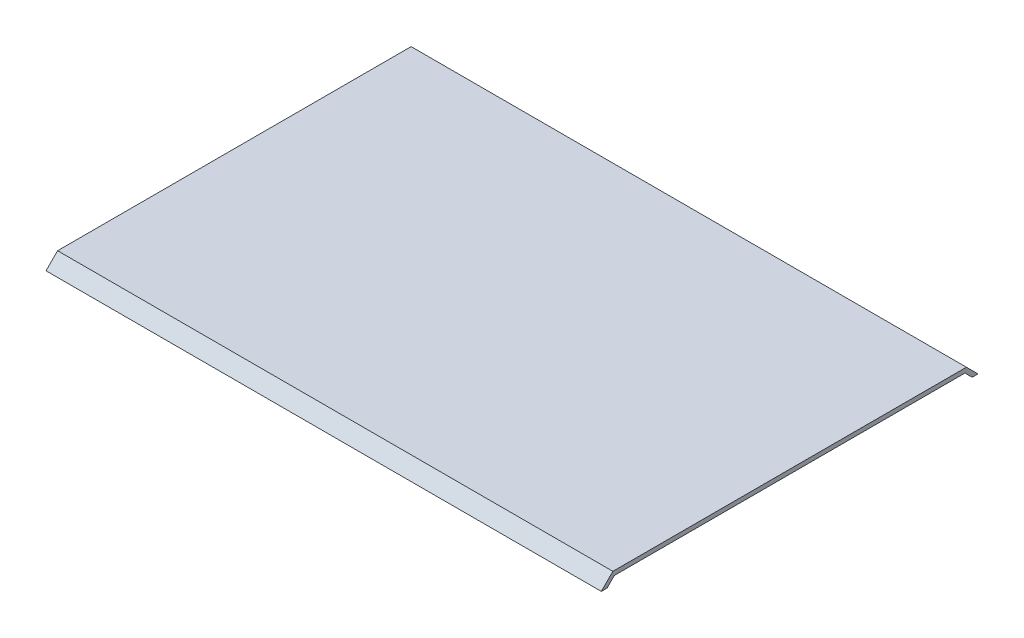
SolidWorks part; units mm, degrees
ref_plane "Front Plane" through (0, 0, 0) normal (0, 0, 1) x (1, 0, 0)
ref_plane "Top Plane" through (0, 0, 0) normal (0, 1, 0) x (1, 0, 0)
ref_plane "Right Plane" through (0, 0, 0) normal (1, 0, 0) x (0, 0, -1)
sketch "Sketch1" plane through (0, 0, 0) normal (1, 0, 0) x (0, 0, -1)
  line L7 (-82.5383, 2.54) -> (82.5383, 2.54)
  line L8 (-71.1083, -2.54) -> (-82.5383, -2.54)
  line L10 (-82.5383, 2.54) -> (-82.5383, -2.54)
  line L11 (82.5383, 2.54) -> (82.5383, -2.54)
  line L12 (82.5383, -2.54) -> (71.1083, -2.54)
  line L14 (-71.1083, -2.54) -> (-71.1083, 0.635)
  line L15 (-71.1083, 0.635) -> (71.1083, 0.635)
  line L16 (71.1083, -2.54) -> (71.1083, 0.635)
  point P9 (0, 0.635)
  point P12 (82.5383, 0)
  dimension "D1" = 1.905
  dimension "D2" = 11.43
  dimension "D5" = 165.0767
  dimension "D6" = 5.08
extrude "Boss-Extrude1" add sketch "Sketch1" along normal blind 243.332
sketch "Sketch2" plane through (0, -2.54, 0) normal (0, -1, 0) x (1, 0, 0)
  line L0 (243.332, 82.5383) -> (0, 82.5383) construction
  line L1 (8.4667, 80.6333) -> (122.7667, 80.6333)
  line L2 (8.4667, 80.6333) -> (8.4667, -80.6333)
  line L3 (8.4667, -80.6333) -> (122.7667, -80.6333)
  line L4 (122.7667, 80.6333) -> (122.7667, -80.6333)
  line L5 (0, 71.1083) -> (0, -71.1083) construction
  line L6 (131.2333, 80.6333) -> (209.4653, 80.6333)
  line L7 (131.2333, 80.6333) -> (131.2333, -80.6333)
  line L8 (131.2333, -80.6333) -> (209.4653, -80.6333)
  line L9 (209.4653, 80.6333) -> (209.4653, -80.6333)
  line L10 (217.932, 80.6333) -> (243.332, 80.6333)
  line L11 (217.932, 80.6333) -> (217.932, -80.6333)
  line L12 (217.932, -80.6333) -> (243.332, -80.6333)
  line L13 (243.332, 80.6333) -> (243.332, -80.6333)
  line L14 (243.332, 82.5383) -> (243.332, 71.1083) construction
  point P4 (8.4667, 0)
  point P17 (131.2333, 0)
  point P24 (217.932, 0)
  point P26 (209.4653, 0)
  dimension "D1" = 1.905
  dimension "D2" = 8.4667
  dimension "D3" = 8.4667
  dimension "D4" = 8.4667
  dimension "D5" = 25.4
  dimension "D7" = 114.3
extrude "Cut-Extrude1" cut sketch "Sketch2" against normal offset from surface (3.175 mm away) 1.905 up to face at (121.666, 2.54, 0)
sketch "Sketch4" plane through (0, -2.54, 0) normal (0, -1, 0) x (1, 0, 0)
  line L0 (4.2333, 78.5167) -> (7.4083, 75.3417)
  line L1 (4.2333, 78.5167) -> (1.0583, 75.3417)
  line L2 (7.4083, 75.3417) -> (4.2333, 72.1667)
  line L3 (1.0583, 75.3417) -> (4.2333, 72.1667)
  line L4 (4.2333, 78.5167) -> (4.2333, 72.1667) construction
  line L5 (7.4083, 75.3417) -> (1.0583, 75.3417) construction
  line L6 (210.5237, 75.3417) -> (213.6987, 78.5167)
  line L7 (8.4667, 71.1083) -> (0, 71.1083) construction
  line L9 (123.825, 75.3417) -> (127, 78.5167)
  line L10 (123.825, 75.3417) -> (127, 72.1667)
  line L11 (127, 78.5167) -> (130.175, 75.3417)
  line L12 (127, 72.1667) -> (130.175, 75.3417)
  line L13 (123.825, 75.3417) -> (130.175, 75.3417) construction
  line L14 (127, 78.5167) -> (127, 72.1667) construction
  line L15 (210.5237, 75.3417) -> (213.6987, 72.1667)
  line L16 (213.6987, 78.5167) -> (216.8737, 75.3417)
  line L17 (213.6987, 72.1667) -> (216.8737, 75.3417)
  line L18 (210.5237, 75.3417) -> (216.8737, 75.3417) construction
  line L19 (213.6987, 78.5167) -> (213.6987, 72.1667) construction
  line L20 (131.2333, 71.1083) -> (122.7667, 71.1083) construction
  line L21 (217.932, 71.1083) -> (209.4653, 71.1083) construction
  line L22 (1.0583, -75.3417) -> (4.2333, -72.1667)
  line L23 (1.0583, -75.3417) -> (4.2333, -78.5167)
  line L24 (4.2333, -72.1667) -> (7.4083, -75.3417)
  line L25 (4.2333, -78.5167) -> (7.4083, -75.3417)
  line L26 (1.0583, -75.3417) -> (7.4083, -75.3417) construction
  line L27 (4.2333, -72.1667) -> (4.2333, -78.5167) construction
  line L28 (123.825, -75.3417) -> (127, -72.1667)
  line L29 (123.825, -75.3417) -> (127, -78.5167)
  line L30 (127, -72.1667) -> (130.175, -75.3417)
  line L31 (127, -78.5167) -> (130.175, -75.3417)
  line L32 (123.825, -75.3417) -> (130.175, -75.3417) construction
  line L33 (127, -72.1667) -> (127, -78.5167) construction
  line L34 (210.5237, -75.3417) -> (213.6987, -72.1667)
  line L35 (210.5237, -75.3417) -> (213.6987, -78.5167)
  line L36 (213.6987, -72.1667) -> (216.8737, -75.3417)
  line L37 (213.6987, -78.5167) -> (216.8737, -75.3417)
  line L38 (210.5237, -75.3417) -> (216.8737, -75.3417) construction
  line L39 (213.6987, -72.1667) -> (213.6987, -78.5167) construction
  line L41 (8.4667, -71.1083) -> (0, -71.1083) construction
  point P1 (4.2333, 75.3417)
  point P3 (4.2333, 71.1083)
  point P12 (127, 75.3417)
  point P13 (213.6987, 75.3417)
  point P19 (127, 71.1083)
  point P26 (213.6987, 71.1083)
  point P28 (4.2333, -75.3417)
  point P29 (127, -75.3417)
  point P30 (213.6987, -75.3417)
  dimension "D1" = 6.35
  dimension "D2" = 4.2333
  dimension "D3" = 4.2333
extrude "Cut-Extrude2" cut sketch "Sketch4" against normal blind 4.2333
chamfer "Chamfer4" distance 0.635 angle 45 48 edges at (2.6458, -2.54, -73.7542) (2.6458, -2.54, -76.9292) (5.8208, -2.54, -76.9292) (5.8208, -2.54, -73.7542) (128.5875, -2.54, -76.9292) (128.5875, -2.54, -73.7542) (125.4125, -2.54, -73.7542) (125.4125, -2.54, -76.9292) (212.1112, -2.54, -76.9292) (212.1112, -2.54, -73.7542) (215.2862, -2.54, -73.7542) (215.2862, -2.54, -76.9292) (5.8208, -2.54, 76.9292) (5.8208, -2.54, 73.7542) (2.6458, -2.54, 76.9292) (2.6458, -2.54, 73.7542) (125.4125, -2.54, 73.7542) (125.4125, -2.54, 76.9292) (128.5875, -2.54, 76.9292) (128.5875, -2.54, 73.7542) (212.1112, -2.54, 73.7542) (212.1112, -2.54, 76.9292) (215.2862, -2.54, 76.9292) (215.2862, -2.54, 73.7542) (212.1112, 1.6933, -73.7542) (215.2862, 1.6933, -73.7542) (215.2862, 1.6933, -76.9292) (212.1112, 1.6933, -76.9292) (125.4125, 1.6933, -73.7542) (128.5875, 1.6933, -73.7542) (128.5875, 1.6933, -76.9292) (125.4125, 1.6933, -76.9292) (2.6458, 1.6933, -73.7542) (5.8208, 1.6933, -73.7542) (5.8208, 1.6933, -76.9292) (2.6458, 1.6933, -76.9292) (5.8208, 1.6933, 76.9292) (5.8208, 1.6933, 73.7542) (2.6458, 1.6933, 73.7542) (2.6458, 1.6933, 76.9292) (125.4125, 1.6933, 76.9292) (128.5875, 1.6933, 76.9292) (128.5875, 1.6933, 73.7542) (125.4125, 1.6933, 73.7542) (212.1112, 1.6933, 76.9292) (215.2862, 1.6933, 76.9292) (215.2862, 1.6933, 73.7542) (212.1112, 1.6933, 73.7542)
chamfer "Chamfer3" distance 3.81 angle 45 6 edges at (65.6167, 0.635, -80.6333) (170.3493, 0.635, -80.6333) (230.632, 0.635, -80.6333) (230.632, 0.635, 80.6333) (170.3493, 0.635, 80.6333) (65.6167, 0.635, 80.6333)
chamfer "Chamfer2" distance 5.08 angle 45 2 edges at (121.666, 2.54, 82.5383) (121.666, 2.54, -82.5383)
